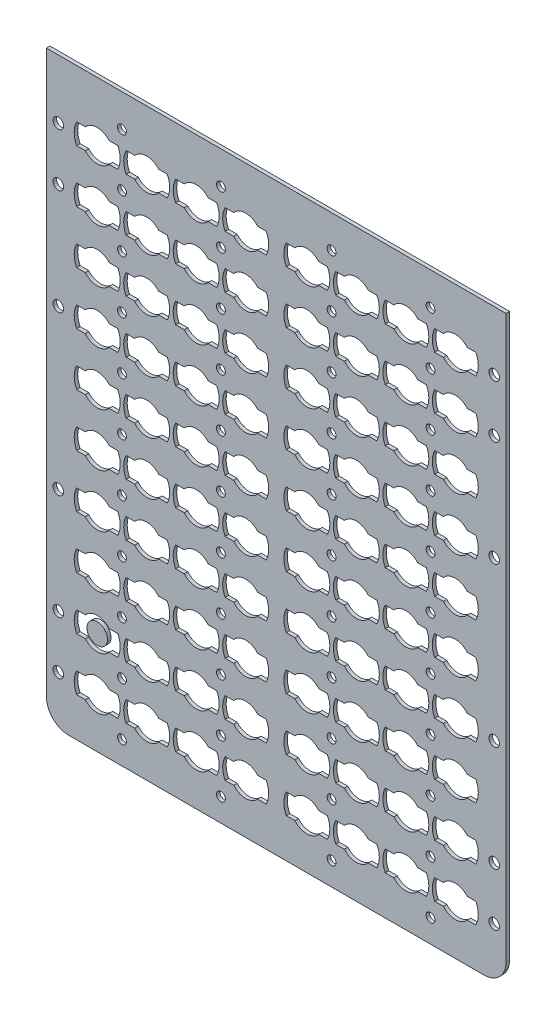
SolidWorks part; units mm, degrees
material "A-Glass Fiber"
ref_plane "X-Y Datum" through (0, 0, 0) normal (0, 0, 1) x (1, 0, 0)
ref_plane "X-Z Datum" through (0, 0, 0) normal (0, 1, 0) x (1, 0, 0)
ref_plane "Y-Z Datum" through (0, 0, 0) normal (1, 0, 0) x (0, 0, -1)
sketch "Sketch1" plane through (0, 0, 0) normal (0, 0, 1) x (1, 0, 0)
  line L0 (0, 10.5) -> (0, 13.63) construction
  line L1 (0, 12.065) -> (-11.77, 12.065) construction
  line L2 (78.318, 0) -> (85.258, 0) construction
  line L3 (10.5, 120.65) -> (12.106, 120.65) construction
  line L4 (0, 110.15) -> (0, 107.02) construction
  line L5 (-10.5, 0) -> (-17.77, 0) construction
  line L6 (-17.77, 0) -> (-17.77, 24.13) construction
  line L7 (81.788, 0) -> (81.788, 240.2038) construction
  line L8 (10.5, 24.13) -> (12.106, 24.13) construction
  line L9 (55.712, 24.13) -> (57.318, 24.13) construction
  line L10 (0, 4.7) -> (0, 19.43) construction
  line L11 (0, -4.7) -> (0, -22.605) construction
  line L12 (-10.5, 0) -> (-23.2, 0) construction
  line L13 (174.076, 217.17) -> (186.776, 217.17) construction
  line L14 (163.576, 227.67) -> (163.576, 244.18) construction
  line L16 (-23.2, -22.605) -> (186.776, -22.605)
  line L17 (-23.2, -22.605) -> (-23.2, 244.18)
  line L18 (-23.2, 244.18) -> (186.776, 244.18)
  line L19 (186.776, -22.605) -> (186.776, 244.18)
  circle A0 centre (0, 0) radius 10.5
  circle A1 centre (22.606, 0) radius 10.5
  circle A2 centre (45.212, 0) radius 10.5
  circle A3 centre (67.818, 0) radius 10.5
  circle A8 centre (22.606, 24.13) radius 10.5
  circle A9 centre (45.212, 24.13) radius 10.5
  circle A10 centre (67.818, 24.13) radius 10.5
  circle A15 centre (22.606, 48.26) radius 10.5
  circle A16 centre (45.212, 48.26) radius 10.5
  circle A17 centre (67.818, 48.26) radius 10.5
  circle A22 centre (22.606, 72.39) radius 10.5
  circle A23 centre (45.212, 72.39) radius 10.5
  circle A24 centre (67.818, 72.39) radius 10.5
  circle A29 centre (22.606, 96.52) radius 10.5
  circle A30 centre (45.212, 96.52) radius 10.5
  circle A31 centre (67.818, 96.52) radius 10.5
  circle A36 centre (22.606, 120.65) radius 10.5
  circle A37 centre (45.212, 120.65) radius 10.5
  circle A38 centre (67.818, 120.65) radius 10.5
  circle A43 centre (22.606, 144.78) radius 10.5
  circle A44 centre (45.212, 144.78) radius 10.5
  circle A45 centre (67.818, 144.78) radius 10.5
  circle A50 centre (22.606, 168.91) radius 10.5
  circle A51 centre (45.212, 168.91) radius 10.5
  circle A52 centre (67.818, 168.91) radius 10.5
  circle A57 centre (22.606, 193.04) radius 10.5
  circle A58 centre (45.212, 193.04) radius 10.5
  circle A59 centre (67.818, 193.04) radius 10.5
  circle A64 centre (22.606, 217.17) radius 10.5
  circle A65 centre (45.212, 217.17) radius 10.5
  circle A66 centre (67.818, 217.17) radius 10.5
  circle A71 centre (0, 24.13) radius 10.5
  circle A72 centre (0, 48.26) radius 10.5
  circle A73 centre (0, 72.39) radius 10.5
  circle A74 centre (0, 96.52) radius 10.5
  circle A75 centre (0, 120.65) radius 10.5
  circle A76 centre (0, 144.78) radius 10.5
  circle A77 centre (0, 168.91) radius 10.5
  circle A78 centre (0, 193.04) radius 10.5
  circle A79 centre (0, 217.17) radius 10.5
  circle A80 centre (95.758, 0) radius 10.5
  circle A81 centre (118.364, 0) radius 10.5
  circle A82 centre (140.97, 0) radius 10.5
  circle A83 centre (163.576, 0) radius 10.5
  circle A84 centre (118.364, 24.13) radius 10.5
  circle A85 centre (140.97, 24.13) radius 10.5
  circle A86 centre (163.576, 24.13) radius 10.5
  circle A87 centre (118.364, 48.26) radius 10.5
  circle A88 centre (140.97, 48.26) radius 10.5
  circle A89 centre (163.576, 48.26) radius 10.5
  circle A90 centre (118.364, 72.39) radius 10.5
  circle A91 centre (140.97, 72.39) radius 10.5
  circle A92 centre (163.576, 72.39) radius 10.5
  circle A93 centre (118.364, 96.52) radius 10.5
  circle A94 centre (140.97, 96.52) radius 10.5
  circle A95 centre (163.576, 96.52) radius 10.5
  circle A96 centre (118.364, 120.65) radius 10.5
  circle A97 centre (140.97, 120.65) radius 10.5
  circle A98 centre (163.576, 120.65) radius 10.5
  circle A99 centre (118.364, 144.78) radius 10.5
  circle A100 centre (140.97, 144.78) radius 10.5
  circle A101 centre (163.576, 144.78) radius 10.5
  circle A102 centre (118.364, 168.91) radius 10.5
  circle A103 centre (140.97, 168.91) radius 10.5
  circle A104 centre (163.576, 168.91) radius 10.5
  circle A105 centre (118.364, 193.04) radius 10.5
  circle A106 centre (140.97, 193.04) radius 10.5
  circle A107 centre (163.576, 193.04) radius 10.5
  circle A108 centre (118.364, 217.17) radius 10.5
  circle A109 centre (140.97, 217.17) radius 10.5
  circle A110 centre (163.576, 217.17) radius 10.5
  circle A111 centre (95.758, 24.13) radius 10.5
  circle A112 centre (95.758, 48.26) radius 10.5
  circle A113 centre (95.758, 72.39) radius 10.5
  circle A114 centre (95.758, 96.52) radius 10.5
  circle A115 centre (95.758, 120.65) radius 10.5
  circle A116 centre (95.758, 144.78) radius 10.5
  circle A117 centre (95.758, 168.91) radius 10.5
  circle A118 centre (95.758, 193.04) radius 10.5
  circle A119 centre (95.758, 217.17) radius 10.5
  circle A120 centre (-17.77, 0) radius 1.5274
  circle A121 centre (-17.77, 24.13) radius 1.5274
  circle A122 centre (-17.77, 48.26) radius 1.5274 [skipped]
  circle A123 centre (-17.77, 72.39) radius 1.5274
  circle A124 centre (-17.77, 96.52) radius 1.5274 [skipped]
  circle A125 centre (-17.77, 120.65) radius 1.5274 [skipped]
  circle A126 centre (-17.77, 144.78) radius 1.5274
  circle A127 centre (-17.77, 168.91) radius 1.5274 [skipped]
  circle A128 centre (-17.77, 193.04) radius 1.5274
  circle A129 centre (-17.77, 217.17) radius 1.5274
  circle A130 centre (181.346, 144.78) radius 1.5274
  circle A131 centre (181.346, 72.39) radius 1.5274
  circle A132 centre (181.346, 0) radius 1.5274
  circle A133 centre (181.346, 217.17) radius 1.5274
  circle A134 centre (11.303, 12.065) radius 2.032
  circle A135 centre (56.515, 12.065) radius 2.032
  circle A136 centre (56.515, 36.195) radius 2.032
  circle A137 centre (56.515, 60.325) radius 2.032
  circle A138 centre (56.515, 84.455) radius 2.032
  circle A139 centre (56.515, 108.585) radius 2.032
  circle A140 centre (56.515, 132.715) radius 2.032
  circle A141 centre (56.515, 156.845) radius 2.032
  circle A142 centre (56.515, 180.975) radius 2.032
  circle A143 centre (56.515, 205.105) radius 2.032
  circle A144 centre (56.515, 229.235) radius 2.032
  circle A145 centre (11.303, 36.195) radius 2.032
  circle A146 centre (11.303, 60.325) radius 2.032
  circle A147 centre (11.303, 84.455) radius 2.032
  circle A148 centre (11.303, 108.585) radius 2.032
  circle A149 centre (11.303, 132.715) radius 2.032
  circle A150 centre (11.303, 156.845) radius 2.032
  circle A151 centre (11.303, 180.975) radius 2.032
  circle A152 centre (11.303, 205.105) radius 2.032
  circle A153 centre (11.303, 229.235) radius 2.032
  circle A154 centre (56.515, -12.065) radius 2.032
  circle A155 centre (11.303, -12.065) radius 2.032
  circle A156 centre (107.061, 229.235) radius 2.032
  circle A157 centre (152.273, 229.235) radius 2.032
  circle A158 centre (152.273, 205.105) radius 2.032
  circle A159 centre (107.061, 205.105) radius 2.032
  circle A160 centre (107.061, 180.975) radius 2.032
  circle A161 centre (152.273, 180.975) radius 2.032
  circle A162 centre (152.273, 156.845) radius 2.032
  circle A163 centre (107.061, 156.845) radius 2.032
  circle A164 centre (107.061, 132.715) radius 2.032
  circle A165 centre (152.273, 132.715) radius 2.032
  circle A166 centre (152.273, 108.585) radius 2.032
  circle A167 centre (107.061, 108.585) radius 2.032
  circle A168 centre (107.061, 84.455) radius 2.032
  circle A169 centre (152.273, 84.455) radius 2.032
  circle A170 centre (152.273, 60.325) radius 2.032
  circle A171 centre (107.061, 60.325) radius 2.032
  circle A172 centre (107.061, 36.195) radius 2.032
  circle A173 centre (152.273, 36.195) radius 2.032
  circle A174 centre (152.273, 12.065) radius 2.032
  circle A175 centre (107.061, 12.065) radius 2.032
  circle A176 centre (107.061, -12.065) radius 2.032
  circle A177 centre (152.273, -12.065) radius 2.032
  circle A178 centre (0, 0) radius 4.7 construction
  circle A179 centre (0, 24.13) radius 4.7 construction
  circle A180 centre (-17.77, 0) radius 6.35 construction
  circle A181 centre (181.346, 24.13) radius 1.5274
  circle A182 centre (181.346, 193.04) radius 1.5274
  dimension "D1" = 4
  dimension "D6" = 21
  dimension "D10" = 2
  dimension "D3" = 11.77
  dimension "D4" = 4
  dimension "D7" = 7.27
  dimension "D9" = 27.94
  dimension "D2" = 10
  dimension "D5" = 10
  dimension "D8" = 10
  dimension "D11" = 10
  dimension "D12" = 2
extrude "Boss-Extrude1" add sketch "Sketch1" along normal blind 1.6
hole_wizard "M4 Clearance Hole1" positions "Sketch2" profile "Sketch3" hole size "M4" standard "ANSI Metric" end condition through all
sketch "Sketch2" plane through (0, 0, 1.6) normal (0, 0, 1) x (1, 0, 0)
  point P0 (-17.77, 217.17)
  point P3 (-17.77, 144.78)
  point P6 (-17.77, 72.39)
  point P9 (-17.77, 0)
  point P12 (181.346, 0)
  point P15 (181.346, 72.39)
  point P18 (181.346, 144.78)
  point P21 (181.346, 217.17)
  point P25 (181.346, 24.13)
  point P28 (-17.77, 24.13)
  point P31 (-17.77, 193.04)
  point P34 (181.346, 193.04)
sketch "Sketch3" plane through (-17.77, 217.17, 1.6) normal (1, 0, 0) x (0, -1, 0)
  line L0 (0, 0) -> (0, 1.6)
  line L1 (0, 1.6) -> (2.4, 1.6)
  line L2 (2.4, 1.6) -> (2.4, 0)
  line L5 (2.4, 0) -> (0, 0)
  line L11 (0, -6.35) -> (0, 107.95) construction
  dimension "Thru Hole Dia." = 4.8
  dimension "Thru Hole Depth" = 1.6
fillet "Fillet1" radius 10.16 2 edges at (186.776, -22.605, 0.8) (-23.2, -22.605, 0.8)
sketch "Sketch5" plane through (0, 0, 1.6) normal (0, 0, 1) x (1, 0, 0)
  line L0 (-5.4544, 4.7) -> (-10.5, 4.7) construction
  line L1 (-10.5, 0) -> (-10.5, 4.7) construction
  line L2 (78.318, 24.13) -> (78.318, 15.2474) construction
  line L3 (5.4544, 19.43) -> (17.1516, 19.43) construction
  line L4 (-5.4544, -4.7) -> (-10.5, -4.7) construction
  line L5 (-10.5, 4.7) -> (-5.4544, 4.7)
  line L6 (-10.5, 4.7) -> (-10.5, 19.43)
  line L7 (-10.5, 19.43) -> (-5.4544, 19.43)
  line L8 (78.318, 4.7) -> (78.318, 19.43)
  line L9 (-10.5, -4.7) -> (-5.4544, -4.7)
  line L10 (-10.5, -4.7) -> (-10.5, -19.43)
  line L11 (-10.5, -19.43) -> (174.076, -19.43)
  line L12 (174.076, -4.7) -> (174.076, -19.43)
  line L13 (5.4544, 19.43) -> (17.1516, 19.43)
  line L14 (73.2724, 19.43) -> (78.318, 19.43) construction
  line L15 (73.2724, 19.43) -> (78.318, 19.43)
  line L16 (50.6664, 19.43) -> (62.3636, 19.43) construction
  line L17 (50.6664, 19.43) -> (62.3636, 19.43)
  line L18 (28.0604, 19.43) -> (39.7576, 19.43) construction
  line L19 (28.0604, 19.43) -> (39.7576, 19.43)
  line L20 (5.4544, 4.7) -> (17.1516, 4.7)
  line L21 (5.4544, -4.7) -> (17.1516, -4.7)
  line L22 (73.2724, 4.7) -> (78.318, 4.7)
  line L23 (50.6664, 4.7) -> (62.3636, 4.7)
  line L24 (28.0604, 4.7) -> (39.7576, 4.7)
  line L25 (28.0604, -4.7) -> (39.7576, -4.7)
  line L26 (50.6664, -4.7) -> (62.3636, -4.7)
  line L27 (73.2724, -4.7) -> (90.3036, -4.7)
  line L28 (81.788, -22.605) -> (81.788, 61.0458) construction
  line L29 (-13.04, -22.605) -> (176.616, -22.605) construction
  line L30 (158.1216, 19.43) -> (146.4244, 19.43)
  line L31 (135.5156, 19.43) -> (123.8184, 19.43)
  line L32 (112.9096, 19.43) -> (101.2124, 19.43)
  line L33 (90.3036, 19.43) -> (85.258, 19.43)
  line L34 (85.258, 4.7) -> (85.258, 19.43)
  line L35 (90.3036, 4.7) -> (85.258, 4.7)
  line L36 (112.9096, 4.7) -> (101.2124, 4.7)
  line L37 (135.5156, 4.7) -> (123.8184, 4.7)
  line L38 (158.1216, 4.7) -> (146.4244, 4.7)
  line L39 (174.076, 4.7) -> (169.0304, 4.7)
  line L40 (174.076, 19.43) -> (169.0304, 19.43)
  line L41 (174.076, 4.7) -> (174.076, 19.43)
  line L42 (101.2124, -4.7) -> (112.9096, -4.7)
  line L43 (123.8184, -4.7) -> (135.5156, -4.7)
  line L44 (146.4244, -4.7) -> (158.1216, -4.7)
  line L45 (169.0304, -4.7) -> (174.076, -4.7)
  line L46 (5.4544, 28.83) -> (17.1516, 28.83)
  line L47 (28.0604, 28.83) -> (39.7576, 28.83)
  line L48 (50.6664, 28.83) -> (62.3636, 28.83)
  line L49 (73.2724, 28.83) -> (78.318, 28.83)
  line L50 (78.318, 28.83) -> (78.318, 43.56)
  line L51 (73.2724, 43.56) -> (78.318, 43.56)
  line L52 (50.6664, 43.56) -> (62.3636, 43.56)
  line L53 (28.0604, 43.56) -> (39.7576, 43.56)
  line L54 (5.4544, 43.56) -> (17.1516, 43.56)
  line L55 (-10.5, 43.56) -> (-5.4544, 43.56)
  line L56 (-10.5, 28.83) -> (-10.5, 43.56)
  line L57 (-10.5, 28.83) -> (-5.4544, 28.83)
  line L58 (158.1216, 43.56) -> (146.4244, 43.56)
  line L59 (135.5156, 43.56) -> (123.8184, 43.56)
  line L60 (112.9096, 43.56) -> (101.2124, 43.56)
  line L61 (90.3036, 43.56) -> (85.258, 43.56)
  line L62 (85.258, 28.83) -> (85.258, 43.56)
  line L63 (90.3036, 28.83) -> (85.258, 28.83)
  line L64 (112.9096, 28.83) -> (101.2124, 28.83)
  line L65 (135.5156, 28.83) -> (123.8184, 28.83)
  line L66 (158.1216, 28.83) -> (146.4244, 28.83)
  line L67 (174.076, 28.83) -> (169.0304, 28.83)
  line L68 (174.076, 28.83) -> (174.076, 43.56)
  line L69 (174.076, 43.56) -> (169.0304, 43.56)
  line L70 (5.4544, 52.96) -> (17.1516, 52.96)
  line L71 (28.0604, 52.96) -> (39.7576, 52.96)
  line L72 (50.6664, 52.96) -> (62.3636, 52.96)
  line L73 (73.2724, 52.96) -> (78.318, 52.96)
  line L74 (78.318, 52.96) -> (78.318, 67.69)
  line L75 (73.2724, 67.69) -> (78.318, 67.69)
  line L76 (50.6664, 67.69) -> (62.3636, 67.69)
  line L77 (28.0604, 67.69) -> (39.7576, 67.69)
  line L78 (5.4544, 67.69) -> (17.1516, 67.69)
  line L79 (-10.5, 67.69) -> (-5.4544, 67.69)
  line L80 (-10.5, 52.96) -> (-10.5, 67.69)
  line L81 (-10.5, 52.96) -> (-5.4544, 52.96)
  line L82 (158.1216, 67.69) -> (146.4244, 67.69)
  line L83 (135.5156, 67.69) -> (123.8184, 67.69)
  line L84 (112.9096, 67.69) -> (101.2124, 67.69)
  line L85 (90.3036, 67.69) -> (85.258, 67.69)
  line L86 (85.258, 52.96) -> (85.258, 67.69)
  line L87 (90.3036, 52.96) -> (85.258, 52.96)
  line L88 (112.9096, 52.96) -> (101.2124, 52.96)
  line L89 (135.5156, 52.96) -> (123.8184, 52.96)
  line L90 (158.1216, 52.96) -> (146.4244, 52.96)
  line L91 (174.076, 52.96) -> (169.0304, 52.96)
  line L92 (174.076, 52.96) -> (174.076, 67.69)
  line L93 (174.076, 67.69) -> (169.0304, 67.69)
  line L94 (5.4544, 77.09) -> (17.1516, 77.09)
  line L95 (28.0604, 77.09) -> (39.7576, 77.09)
  line L96 (50.6664, 77.09) -> (62.3636, 77.09)
  line L97 (73.2724, 77.09) -> (78.318, 77.09)
  line L98 (78.318, 77.09) -> (78.318, 91.82)
  line L99 (73.2724, 91.82) -> (78.318, 91.82)
  line L100 (50.6664, 91.82) -> (62.3636, 91.82)
  line L101 (28.0604, 91.82) -> (39.7576, 91.82)
  line L102 (5.4544, 91.82) -> (17.1516, 91.82)
  line L103 (-10.5, 91.82) -> (-5.4544, 91.82)
  line L104 (-10.5, 77.09) -> (-10.5, 91.82)
  line L105 (-10.5, 77.09) -> (-5.4544, 77.09)
  line L106 (158.1216, 91.82) -> (146.4244, 91.82)
  line L107 (135.5156, 91.82) -> (123.8184, 91.82)
  line L108 (112.9096, 91.82) -> (101.2124, 91.82)
  line L109 (90.3036, 91.82) -> (85.258, 91.82)
  line L110 (85.258, 77.09) -> (85.258, 91.82)
  line L111 (90.3036, 77.09) -> (85.258, 77.09)
  line L112 (112.9096, 77.09) -> (101.2124, 77.09)
  line L113 (135.5156, 77.09) -> (123.8184, 77.09)
  line L114 (158.1216, 77.09) -> (146.4244, 77.09)
  line L115 (174.076, 77.09) -> (169.0304, 77.09)
  line L116 (174.076, 77.09) -> (174.076, 91.82)
  line L117 (174.076, 91.82) -> (169.0304, 91.82)
  line L118 (5.4544, 101.22) -> (17.1516, 101.22)
  line L119 (28.0604, 101.22) -> (39.7576, 101.22)
  line L120 (50.6664, 101.22) -> (62.3636, 101.22)
  line L121 (73.2724, 101.22) -> (78.318, 101.22)
  line L122 (78.318, 101.22) -> (78.318, 115.95)
  line L123 (73.2724, 115.95) -> (78.318, 115.95)
  line L124 (50.6664, 115.95) -> (62.3636, 115.95)
  line L125 (28.0604, 115.95) -> (39.7576, 115.95)
  line L126 (5.4544, 115.95) -> (17.1516, 115.95)
  line L127 (-10.5, 115.95) -> (-5.4544, 115.95)
  line L128 (-10.5, 101.22) -> (-10.5, 115.95)
  line L129 (-10.5, 101.22) -> (-5.4544, 101.22)
  line L130 (158.1216, 115.95) -> (146.4244, 115.95)
  line L131 (135.5156, 115.95) -> (123.8184, 115.95)
  line L132 (112.9096, 115.95) -> (101.2124, 115.95)
  line L133 (90.3036, 115.95) -> (85.258, 115.95)
  line L134 (85.258, 101.22) -> (85.258, 115.95)
  line L135 (90.3036, 101.22) -> (85.258, 101.22)
  line L136 (112.9096, 101.22) -> (101.2124, 101.22)
  line L137 (135.5156, 101.22) -> (123.8184, 101.22)
  line L138 (158.1216, 101.22) -> (146.4244, 101.22)
  line L139 (174.076, 101.22) -> (169.0304, 101.22)
  line L140 (174.076, 101.22) -> (174.076, 115.95)
  line L141 (174.076, 115.95) -> (169.0304, 115.95)
  line L142 (5.4544, 125.35) -> (17.1516, 125.35)
  line L143 (28.0604, 125.35) -> (39.7576, 125.35)
  line L144 (50.6664, 125.35) -> (62.3636, 125.35)
  line L145 (73.2724, 125.35) -> (78.318, 125.35)
  line L146 (78.318, 125.35) -> (78.318, 140.08)
  line L147 (73.2724, 140.08) -> (78.318, 140.08)
  line L148 (50.6664, 140.08) -> (62.3636, 140.08)
  line L149 (28.0604, 140.08) -> (39.7576, 140.08)
  line L150 (5.4544, 140.08) -> (17.1516, 140.08)
  line L151 (-10.5, 140.08) -> (-5.4544, 140.08)
  line L152 (-10.5, 125.35) -> (-10.5, 140.08)
  line L153 (-10.5, 125.35) -> (-5.4544, 125.35)
  line L154 (158.1216, 140.08) -> (146.4244, 140.08)
  line L155 (135.5156, 140.08) -> (123.8184, 140.08)
  line L156 (112.9096, 140.08) -> (101.2124, 140.08)
  line L157 (90.3036, 140.08) -> (85.258, 140.08)
  line L158 (85.258, 125.35) -> (85.258, 140.08)
  line L159 (90.3036, 125.35) -> (85.258, 125.35)
  line L160 (112.9096, 125.35) -> (101.2124, 125.35)
  line L161 (135.5156, 125.35) -> (123.8184, 125.35)
  line L162 (158.1216, 125.35) -> (146.4244, 125.35)
  line L163 (174.076, 125.35) -> (169.0304, 125.35)
  line L164 (174.076, 125.35) -> (174.076, 140.08)
  line L165 (174.076, 140.08) -> (169.0304, 140.08)
  line L166 (5.4544, 149.48) -> (17.1516, 149.48)
  line L167 (28.0604, 149.48) -> (39.7576, 149.48)
  line L168 (50.6664, 149.48) -> (62.3636, 149.48)
  line L169 (73.2724, 149.48) -> (78.318, 149.48)
  line L170 (78.318, 149.48) -> (78.318, 164.21)
  line L171 (73.2724, 164.21) -> (78.318, 164.21)
  line L172 (50.6664, 164.21) -> (62.3636, 164.21)
  line L173 (28.0604, 164.21) -> (39.7576, 164.21)
  line L174 (5.4544, 164.21) -> (17.1516, 164.21)
  line L175 (-10.5, 164.21) -> (-5.4544, 164.21)
  line L176 (-10.5, 149.48) -> (-10.5, 164.21)
  line L177 (-10.5, 149.48) -> (-5.4544, 149.48)
  line L178 (158.1216, 164.21) -> (146.4244, 164.21)
  line L179 (135.5156, 164.21) -> (123.8184, 164.21)
  line L180 (112.9096, 164.21) -> (101.2124, 164.21)
  line L181 (90.3036, 164.21) -> (85.258, 164.21)
  line L182 (85.258, 149.48) -> (85.258, 164.21)
  line L183 (90.3036, 149.48) -> (85.258, 149.48)
  line L184 (112.9096, 149.48) -> (101.2124, 149.48)
  line L185 (135.5156, 149.48) -> (123.8184, 149.48)
  line L186 (158.1216, 149.48) -> (146.4244, 149.48)
  line L187 (174.076, 149.48) -> (169.0304, 149.48)
  line L188 (174.076, 149.48) -> (174.076, 164.21)
  line L189 (174.076, 164.21) -> (169.0304, 164.21)
  line L190 (5.4544, 173.61) -> (17.1516, 173.61)
  line L191 (28.0604, 173.61) -> (39.7576, 173.61)
  line L192 (50.6664, 173.61) -> (62.3636, 173.61)
  line L193 (73.2724, 173.61) -> (78.318, 173.61)
  line L194 (78.318, 173.61) -> (78.318, 188.34)
  line L195 (73.2724, 188.34) -> (78.318, 188.34)
  line L196 (50.6664, 188.34) -> (62.3636, 188.34)
  line L197 (28.0604, 188.34) -> (39.7576, 188.34)
  line L198 (5.4544, 188.34) -> (17.1516, 188.34)
  line L199 (-10.5, 188.34) -> (-5.4544, 188.34)
  line L200 (-10.5, 173.61) -> (-10.5, 188.34)
  line L201 (-10.5, 173.61) -> (-5.4544, 173.61)
  line L202 (158.1216, 188.34) -> (146.4244, 188.34)
  line L203 (135.5156, 188.34) -> (123.8184, 188.34)
  line L204 (112.9096, 188.34) -> (101.2124, 188.34)
  line L205 (90.3036, 188.34) -> (85.258, 188.34)
  line L206 (85.258, 173.61) -> (85.258, 188.34)
  line L207 (90.3036, 173.61) -> (85.258, 173.61)
  line L208 (112.9096, 173.61) -> (101.2124, 173.61)
  line L209 (135.5156, 173.61) -> (123.8184, 173.61)
  line L210 (158.1216, 173.61) -> (146.4244, 173.61)
  line L211 (174.076, 173.61) -> (169.0304, 173.61)
  line L212 (174.076, 173.61) -> (174.076, 188.34)
  line L213 (174.076, 188.34) -> (169.0304, 188.34)
  line L214 (5.4544, 197.74) -> (17.1516, 197.74)
  line L215 (28.0604, 197.74) -> (39.7576, 197.74)
  line L216 (50.6664, 197.74) -> (62.3636, 197.74)
  line L217 (73.2724, 197.74) -> (78.318, 197.74)
  line L218 (78.318, 197.74) -> (78.318, 212.47)
  line L219 (73.2724, 212.47) -> (78.318, 212.47)
  line L220 (50.6664, 212.47) -> (62.3636, 212.47)
  line L221 (28.0604, 212.47) -> (39.7576, 212.47)
  line L222 (5.4544, 212.47) -> (17.1516, 212.47)
  line L223 (-10.5, 212.47) -> (-5.4544, 212.47)
  line L224 (-10.5, 197.74) -> (-10.5, 212.47)
  line L225 (-10.5, 197.74) -> (-5.4544, 197.74)
  line L226 (158.1216, 212.47) -> (146.4244, 212.47)
  line L227 (135.5156, 212.47) -> (123.8184, 212.47)
  line L228 (112.9096, 212.47) -> (101.2124, 212.47)
  line L229 (90.3036, 212.47) -> (85.258, 212.47)
  line L230 (85.258, 197.74) -> (85.258, 212.47)
  line L231 (90.3036, 197.74) -> (85.258, 197.74)
  line L232 (112.9096, 197.74) -> (101.2124, 197.74)
  line L233 (135.5156, 197.74) -> (123.8184, 197.74)
  line L234 (158.1216, 197.74) -> (146.4244, 197.74)
  line L235 (174.076, 197.74) -> (169.0304, 197.74)
  line L236 (174.076, 197.74) -> (174.076, 212.47)
  line L237 (174.076, 212.47) -> (169.0304, 212.47)
  line L238 (67.818, 227.67) -> (67.818, -10.5) construction
  line L239 (-36.163, 227.67) -> (-36.163, -10.5) construction
  line L240 (-36.163, 108.585) -> (226.9645, 108.585) construction
  line L241 (123.8184, 221.87) -> (135.5156, 221.87)
  line L242 (101.2124, 221.87) -> (112.9096, 221.87)
  line L243 (73.2724, 221.87) -> (90.3036, 221.87)
  line L244 (50.6664, 221.87) -> (62.3636, 221.87)
  line L245 (28.0604, 221.87) -> (39.7576, 221.87)
  line L246 (5.4544, 221.87) -> (17.1516, 221.87)
  line L247 (-10.5, 221.87) -> (-5.4544, 221.87)
  line L248 (-10.5, 221.87) -> (-10.5, 236.6)
  line L249 (-10.5, 236.6) -> (174.076, 236.6)
  line L250 (174.076, 221.87) -> (174.076, 236.6)
  line L251 (169.0304, 221.87) -> (174.076, 221.87)
  line L252 (146.4244, 221.87) -> (158.1216, 221.87)
  circle A0 centre (0, 0) radius 4.7 construction
  circle A1 centre (0, 24.13) radius 4.7
  circle A2 centre (11.303, -12.065) radius 2.032
  circle A3 centre (56.515, -12.065) radius 2.032
  circle A4 centre (0, 0) radius 10.5 construction
  circle A5 centre (67.818, 24.13) radius 10.5 construction
  circle A6 centre (11.303, 12.065) radius 2.032
  circle A7 centre (56.515, 12.065) radius 2.032
  circle A8 centre (107.061, -12.065) radius 2.032
  circle A9 centre (152.273, -12.065) radius 2.032
  arc A10 (5.4544, 4.7) -> (-5.4544, 4.7) centre (0, 0) ccw
  arc A11 (-5.4544, 19.43) -> (5.4544, 19.43) centre (0, 24.13) ccw
  arc A12 (17.1516, 19.43) -> (28.0604, 19.43) centre (22.606, 24.13) ccw
  arc A13 (17.1516, -4.7) -> (28.0604, -4.7) centre (22.606, 0) ccw
  arc A14 (39.7576, 19.43) -> (50.6664, 19.43) centre (45.212, 24.13) ccw
  arc A15 (39.7576, -4.7) -> (50.6664, -4.7) centre (45.212, 0) ccw
  arc A16 (62.3636, 19.43) -> (73.2724, 19.43) centre (67.818, 24.13) ccw
  arc A17 (62.3636, -4.7) -> (73.2724, -4.7) centre (67.818, 0) ccw
  circle A18 centre (0, 24.13) radius 7.2 construction
  circle A19 centre (0, 0) radius 7.2 construction
  arc A20 (-5.4544, -4.7) -> (5.4544, -4.7) centre (0, 0) ccw
  arc A21 (28.0604, 4.7) -> (17.1516, 4.7) centre (22.606, 0) ccw
  arc A22 (50.6664, 4.7) -> (39.7576, 4.7) centre (45.212, 0) ccw
  arc A23 (73.2724, 4.7) -> (62.3636, 4.7) centre (67.818, 0) ccw
  arc A24 (101.2124, -4.7) -> (90.3036, -4.7) centre (95.758, 0) cw
  arc A25 (123.8184, -4.7) -> (112.9096, -4.7) centre (118.364, 0) cw
  arc A26 (146.4244, -4.7) -> (135.5156, -4.7) centre (140.97, 0) cw
  arc A27 (169.0304, -4.7) -> (158.1216, -4.7) centre (163.576, 0) cw
  circle A28 centre (107.061, 12.065) radius 2.032
  circle A29 centre (152.273, 12.065) radius 2.032
  arc A30 (146.4244, 19.43) -> (135.5156, 19.43) centre (140.97, 24.13) cw
  arc A31 (123.8184, 19.43) -> (112.9096, 19.43) centre (118.364, 24.13) cw
  arc A32 (101.2124, 19.43) -> (90.3036, 19.43) centre (95.758, 24.13) cw
  arc A33 (90.3036, 4.7) -> (101.2124, 4.7) centre (95.758, 0) cw
  arc A34 (112.9096, 4.7) -> (123.8184, 4.7) centre (118.364, 0) cw
  arc A35 (135.5156, 4.7) -> (146.4244, 4.7) centre (140.97, 0) cw
  arc A36 (158.1216, 4.7) -> (169.0304, 4.7) centre (163.576, 0) cw
  arc A37 (169.0304, 19.43) -> (158.1216, 19.43) centre (163.576, 24.13) cw
  arc A38 (28.0604, 28.83) -> (17.1516, 28.83) centre (22.606, 24.13) ccw
  arc A39 (50.6664, 28.83) -> (39.7576, 28.83) centre (45.212, 24.13) ccw
  arc A40 (73.2724, 28.83) -> (62.3636, 28.83) centre (67.818, 24.13) ccw
  arc A41 (62.3636, 43.56) -> (73.2724, 43.56) centre (67.818, 48.26) ccw
  arc A42 (39.7576, 43.56) -> (50.6664, 43.56) centre (45.212, 48.26) ccw
  arc A43 (17.1516, 43.56) -> (28.0604, 43.56) centre (22.606, 48.26) ccw
  arc A44 (-5.4544, 43.56) -> (5.4544, 43.56) centre (0, 48.26) ccw
  arc A45 (5.4544, 28.83) -> (-5.4544, 28.83) centre (0, 24.13) ccw
  arc A46 (146.4244, 43.56) -> (135.5156, 43.56) centre (140.97, 48.26) cw
  arc A47 (123.8184, 43.56) -> (112.9096, 43.56) centre (118.364, 48.26) cw
  arc A48 (101.2124, 43.56) -> (90.3036, 43.56) centre (95.758, 48.26) cw
  arc A49 (90.3036, 28.83) -> (101.2124, 28.83) centre (95.758, 24.13) cw
  arc A50 (112.9096, 28.83) -> (123.8184, 28.83) centre (118.364, 24.13) cw
  arc A51 (135.5156, 28.83) -> (146.4244, 28.83) centre (140.97, 24.13) cw
  arc A52 (158.1216, 28.83) -> (169.0304, 28.83) centre (163.576, 24.13) cw
  arc A53 (169.0304, 43.56) -> (158.1216, 43.56) centre (163.576, 48.26) cw
  circle A54 centre (11.303, 36.195) radius 2.032
  circle A55 centre (56.515, 36.195) radius 2.032
  circle A56 centre (107.061, 36.195) radius 2.032
  circle A57 centre (152.273, 36.195) radius 2.032
  arc A58 (28.0604, 52.96) -> (17.1516, 52.96) centre (22.606, 48.26) ccw
  arc A59 (50.6664, 52.96) -> (39.7576, 52.96) centre (45.212, 48.26) ccw
  arc A60 (73.2724, 52.96) -> (62.3636, 52.96) centre (67.818, 48.26) ccw
  arc A61 (62.3636, 67.69) -> (73.2724, 67.69) centre (67.818, 72.39) ccw
  arc A62 (39.7576, 67.69) -> (50.6664, 67.69) centre (45.212, 72.39) ccw
  arc A63 (17.1516, 67.69) -> (28.0604, 67.69) centre (22.606, 72.39) ccw
  arc A64 (-5.4544, 67.69) -> (5.4544, 67.69) centre (0, 72.39) ccw
  arc A65 (5.4544, 52.96) -> (-5.4544, 52.96) centre (0, 48.26) ccw
  arc A66 (146.4244, 67.69) -> (135.5156, 67.69) centre (140.97, 72.39) cw
  arc A67 (123.8184, 67.69) -> (112.9096, 67.69) centre (118.364, 72.39) cw
  arc A68 (101.2124, 67.69) -> (90.3036, 67.69) centre (95.758, 72.39) cw
  arc A69 (90.3036, 52.96) -> (101.2124, 52.96) centre (95.758, 48.26) cw
  arc A70 (112.9096, 52.96) -> (123.8184, 52.96) centre (118.364, 48.26) cw
  arc A71 (135.5156, 52.96) -> (146.4244, 52.96) centre (140.97, 48.26) cw
  arc A72 (158.1216, 52.96) -> (169.0304, 52.96) centre (163.576, 48.26) cw
  arc A73 (169.0304, 67.69) -> (158.1216, 67.69) centre (163.576, 72.39) cw
  circle A74 centre (11.303, 60.325) radius 2.032
  circle A75 centre (56.515, 60.325) radius 2.032
  circle A76 centre (107.061, 60.325) radius 2.032
  circle A77 centre (152.273, 60.325) radius 2.032
  arc A78 (28.0604, 77.09) -> (17.1516, 77.09) centre (22.606, 72.39) ccw
  arc A79 (50.6664, 77.09) -> (39.7576, 77.09) centre (45.212, 72.39) ccw
  arc A80 (73.2724, 77.09) -> (62.3636, 77.09) centre (67.818, 72.39) ccw
  arc A81 (62.3636, 91.82) -> (73.2724, 91.82) centre (67.818, 96.52) ccw
  arc A82 (39.7576, 91.82) -> (50.6664, 91.82) centre (45.212, 96.52) ccw
  arc A83 (17.1516, 91.82) -> (28.0604, 91.82) centre (22.606, 96.52) ccw
  arc A84 (-5.4544, 91.82) -> (5.4544, 91.82) centre (0, 96.52) ccw
  arc A85 (5.4544, 77.09) -> (-5.4544, 77.09) centre (0, 72.39) ccw
  arc A86 (146.4244, 91.82) -> (135.5156, 91.82) centre (140.97, 96.52) cw
  arc A87 (123.8184, 91.82) -> (112.9096, 91.82) centre (118.364, 96.52) cw
  arc A88 (101.2124, 91.82) -> (90.3036, 91.82) centre (95.758, 96.52) cw
  arc A89 (90.3036, 77.09) -> (101.2124, 77.09) centre (95.758, 72.39) cw
  arc A90 (112.9096, 77.09) -> (123.8184, 77.09) centre (118.364, 72.39) cw
  arc A91 (135.5156, 77.09) -> (146.4244, 77.09) centre (140.97, 72.39) cw
  arc A92 (158.1216, 77.09) -> (169.0304, 77.09) centre (163.576, 72.39) cw
  arc A93 (169.0304, 91.82) -> (158.1216, 91.82) centre (163.576, 96.52) cw
  circle A94 centre (11.303, 84.455) radius 2.032
  circle A95 centre (56.515, 84.455) radius 2.032
  circle A96 centre (107.061, 84.455) radius 2.032
  circle A97 centre (152.273, 84.455) radius 2.032
  arc A98 (28.0604, 101.22) -> (17.1516, 101.22) centre (22.606, 96.52) ccw
  arc A99 (50.6664, 101.22) -> (39.7576, 101.22) centre (45.212, 96.52) ccw
  arc A100 (73.2724, 101.22) -> (62.3636, 101.22) centre (67.818, 96.52) ccw
  arc A101 (62.3636, 115.95) -> (73.2724, 115.95) centre (67.818, 120.65) ccw
  arc A102 (39.7576, 115.95) -> (50.6664, 115.95) centre (45.212, 120.65) ccw
  arc A103 (17.1516, 115.95) -> (28.0604, 115.95) centre (22.606, 120.65) ccw
  arc A104 (-5.4544, 115.95) -> (5.4544, 115.95) centre (0, 120.65) ccw
  arc A105 (5.4544, 101.22) -> (-5.4544, 101.22) centre (0, 96.52) ccw
  arc A106 (146.4244, 115.95) -> (135.5156, 115.95) centre (140.97, 120.65) cw
  arc A107 (123.8184, 115.95) -> (112.9096, 115.95) centre (118.364, 120.65) cw
  arc A108 (101.2124, 115.95) -> (90.3036, 115.95) centre (95.758, 120.65) cw
  arc A109 (90.3036, 101.22) -> (101.2124, 101.22) centre (95.758, 96.52) cw
  arc A110 (112.9096, 101.22) -> (123.8184, 101.22) centre (118.364, 96.52) cw
  arc A111 (135.5156, 101.22) -> (146.4244, 101.22) centre (140.97, 96.52) cw
  arc A112 (158.1216, 101.22) -> (169.0304, 101.22) centre (163.576, 96.52) cw
  arc A113 (169.0304, 115.95) -> (158.1216, 115.95) centre (163.576, 120.65) cw
  circle A114 centre (11.303, 108.585) radius 2.032
  circle A115 centre (56.515, 108.585) radius 2.032
  circle A116 centre (107.061, 108.585) radius 2.032
  circle A117 centre (152.273, 108.585) radius 2.032
  arc A118 (28.0604, 125.35) -> (17.1516, 125.35) centre (22.606, 120.65) ccw
  arc A119 (50.6664, 125.35) -> (39.7576, 125.35) centre (45.212, 120.65) ccw
  arc A120 (73.2724, 125.35) -> (62.3636, 125.35) centre (67.818, 120.65) ccw
  arc A121 (62.3636, 140.08) -> (73.2724, 140.08) centre (67.818, 144.78) ccw
  arc A122 (39.7576, 140.08) -> (50.6664, 140.08) centre (45.212, 144.78) ccw
  arc A123 (17.1516, 140.08) -> (28.0604, 140.08) centre (22.606, 144.78) ccw
  arc A124 (-5.4544, 140.08) -> (5.4544, 140.08) centre (0, 144.78) ccw
  arc A125 (5.4544, 125.35) -> (-5.4544, 125.35) centre (0, 120.65) ccw
  arc A126 (146.4244, 140.08) -> (135.5156, 140.08) centre (140.97, 144.78) cw
  arc A127 (123.8184, 140.08) -> (112.9096, 140.08) centre (118.364, 144.78) cw
  arc A128 (101.2124, 140.08) -> (90.3036, 140.08) centre (95.758, 144.78) cw
  arc A129 (90.3036, 125.35) -> (101.2124, 125.35) centre (95.758, 120.65) cw
  arc A130 (112.9096, 125.35) -> (123.8184, 125.35) centre (118.364, 120.65) cw
  arc A131 (135.5156, 125.35) -> (146.4244, 125.35) centre (140.97, 120.65) cw
  arc A132 (158.1216, 125.35) -> (169.0304, 125.35) centre (163.576, 120.65) cw
  arc A133 (169.0304, 140.08) -> (158.1216, 140.08) centre (163.576, 144.78) cw
  circle A134 centre (11.303, 132.715) radius 2.032
  circle A135 centre (56.515, 132.715) radius 2.032
  circle A136 centre (107.061, 132.715) radius 2.032
  circle A137 centre (152.273, 132.715) radius 2.032
  arc A138 (28.0604, 149.48) -> (17.1516, 149.48) centre (22.606, 144.78) ccw
  arc A139 (50.6664, 149.48) -> (39.7576, 149.48) centre (45.212, 144.78) ccw
  arc A140 (73.2724, 149.48) -> (62.3636, 149.48) centre (67.818, 144.78) ccw
  arc A141 (62.3636, 164.21) -> (73.2724, 164.21) centre (67.818, 168.91) ccw
  arc A142 (39.7576, 164.21) -> (50.6664, 164.21) centre (45.212, 168.91) ccw
  arc A143 (17.1516, 164.21) -> (28.0604, 164.21) centre (22.606, 168.91) ccw
  arc A144 (-5.4544, 164.21) -> (5.4544, 164.21) centre (0, 168.91) ccw
  arc A145 (5.4544, 149.48) -> (-5.4544, 149.48) centre (0, 144.78) ccw
  arc A146 (146.4244, 164.21) -> (135.5156, 164.21) centre (140.97, 168.91) cw
  arc A147 (123.8184, 164.21) -> (112.9096, 164.21) centre (118.364, 168.91) cw
  arc A148 (101.2124, 164.21) -> (90.3036, 164.21) centre (95.758, 168.91) cw
  arc A149 (90.3036, 149.48) -> (101.2124, 149.48) centre (95.758, 144.78) cw
  arc A150 (112.9096, 149.48) -> (123.8184, 149.48) centre (118.364, 144.78) cw
  arc A151 (135.5156, 149.48) -> (146.4244, 149.48) centre (140.97, 144.78) cw
  arc A152 (158.1216, 149.48) -> (169.0304, 149.48) centre (163.576, 144.78) cw
  arc A153 (169.0304, 164.21) -> (158.1216, 164.21) centre (163.576, 168.91) cw
  circle A154 centre (11.303, 156.845) radius 2.032
  circle A155 centre (56.515, 156.845) radius 2.032
  circle A156 centre (107.061, 156.845) radius 2.032
  circle A157 centre (152.273, 156.845) radius 2.032
  arc A158 (28.0604, 173.61) -> (17.1516, 173.61) centre (22.606, 168.91) ccw
  arc A159 (50.6664, 173.61) -> (39.7576, 173.61) centre (45.212, 168.91) ccw
  arc A160 (73.2724, 173.61) -> (62.3636, 173.61) centre (67.818, 168.91) ccw
  arc A161 (62.3636, 188.34) -> (73.2724, 188.34) centre (67.818, 193.04) ccw
  arc A162 (39.7576, 188.34) -> (50.6664, 188.34) centre (45.212, 193.04) ccw
  arc A163 (17.1516, 188.34) -> (28.0604, 188.34) centre (22.606, 193.04) ccw
  arc A164 (-5.4544, 188.34) -> (5.4544, 188.34) centre (0, 193.04) ccw
  arc A165 (5.4544, 173.61) -> (-5.4544, 173.61) centre (0, 168.91) ccw
  arc A166 (146.4244, 188.34) -> (135.5156, 188.34) centre (140.97, 193.04) cw
  arc A167 (123.8184, 188.34) -> (112.9096, 188.34) centre (118.364, 193.04) cw
  arc A168 (101.2124, 188.34) -> (90.3036, 188.34) centre (95.758, 193.04) cw
  arc A169 (90.3036, 173.61) -> (101.2124, 173.61) centre (95.758, 168.91) cw
  arc A170 (112.9096, 173.61) -> (123.8184, 173.61) centre (118.364, 168.91) cw
  arc A171 (135.5156, 173.61) -> (146.4244, 173.61) centre (140.97, 168.91) cw
  arc A172 (158.1216, 173.61) -> (169.0304, 173.61) centre (163.576, 168.91) cw
  arc A173 (169.0304, 188.34) -> (158.1216, 188.34) centre (163.576, 193.04) cw
  circle A174 centre (11.303, 180.975) radius 2.032
  circle A175 centre (56.515, 180.975) radius 2.032
  circle A176 centre (107.061, 180.975) radius 2.032
  circle A177 centre (152.273, 180.975) radius 2.032
  arc A178 (28.0604, 197.74) -> (17.1516, 197.74) centre (22.606, 193.04) ccw
  arc A179 (50.6664, 197.74) -> (39.7576, 197.74) centre (45.212, 193.04) ccw
  arc A180 (73.2724, 197.74) -> (62.3636, 197.74) centre (67.818, 193.04) ccw
  arc A181 (62.3636, 212.47) -> (73.2724, 212.47) centre (67.818, 217.17) ccw
  arc A182 (39.7576, 212.47) -> (50.6664, 212.47) centre (45.212, 217.17) ccw
  arc A183 (17.1516, 212.47) -> (28.0604, 212.47) centre (22.606, 217.17) ccw
  arc A184 (-5.4544, 212.47) -> (5.4544, 212.47) centre (0, 217.17) ccw
  arc A185 (5.4544, 197.74) -> (-5.4544, 197.74) centre (0, 193.04) ccw
  arc A186 (146.4244, 212.47) -> (135.5156, 212.47) centre (140.97, 217.17) cw
  arc A187 (123.8184, 212.47) -> (112.9096, 212.47) centre (118.364, 217.17) cw
  arc A188 (101.2124, 212.47) -> (90.3036, 212.47) centre (95.758, 217.17) cw
  arc A189 (90.3036, 197.74) -> (101.2124, 197.74) centre (95.758, 193.04) cw
  arc A190 (112.9096, 197.74) -> (123.8184, 197.74) centre (118.364, 193.04) cw
  arc A191 (135.5156, 197.74) -> (146.4244, 197.74) centre (140.97, 193.04) cw
  arc A192 (158.1216, 197.74) -> (169.0304, 197.74) centre (163.576, 193.04) cw
  arc A193 (169.0304, 212.47) -> (158.1216, 212.47) centre (163.576, 217.17) cw
  circle A194 centre (11.303, 205.105) radius 2.032
  circle A195 centre (56.515, 205.105) radius 2.032
  circle A196 centre (107.061, 205.105) radius 2.032
  circle A197 centre (152.273, 205.105) radius 2.032
  circle A198 centre (67.818, 217.17) radius 10.5 construction
  circle A199 centre (67.818, 0) radius 10.5 construction
  arc A200 (146.4244, 221.87) -> (135.5156, 221.87) centre (140.97, 217.17) ccw
  arc A201 (123.8184, 221.87) -> (112.9096, 221.87) centre (118.364, 217.17) ccw
  arc A202 (101.2124, 221.87) -> (90.3036, 221.87) centre (95.758, 217.17) ccw
  arc A203 (62.3636, 221.87) -> (73.2724, 221.87) centre (67.818, 217.17) cw
  arc A204 (39.7576, 221.87) -> (50.6664, 221.87) centre (45.212, 217.17) cw
  arc A205 (17.1516, 221.87) -> (28.0604, 221.87) centre (22.606, 217.17) cw
  arc A206 (-5.4544, 221.87) -> (5.4544, 221.87) centre (0, 217.17) cw
  arc A207 (169.0304, 221.87) -> (158.1216, 221.87) centre (163.576, 217.17) ccw
  circle A208 centre (11.303, 229.235) radius 2.032
  circle A209 centre (56.515, 229.235) radius 2.032
  circle A210 centre (107.061, 229.235) radius 2.032
  circle A211 centre (152.273, 229.235) radius 2.032
  dimension "D1" = 2.5
  dimension "D2" = 2.5
  dimension "D3" = 4
  dimension "D4" = 9
extrude "Boss-Extrude2" add sketch "Sketch5" against normal through all
